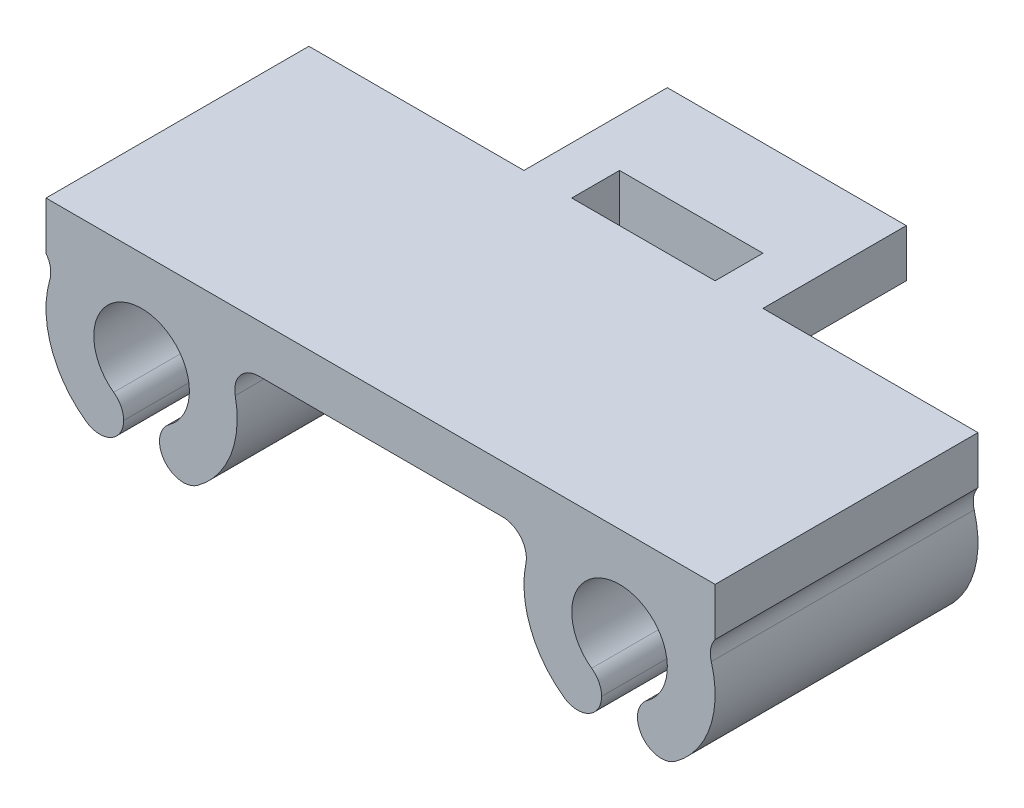
SolidWorks part; units mm, degrees
ref_plane "Front Plane" through (0, 0, 0) normal (0, 0, 1) x (1, 0, 0)
ref_plane "Top Plane" through (0, 0, 0) normal (0, 1, 0) x (1, 0, 0)
ref_plane "Right Plane" through (0, 0, 0) normal (1, 0, 0) x (0, 0, -1)
sketch "Sketch1" plane through (0, 0, 0) normal (0, 1, 0) x (1, 0, 0)
  line L1 (-14, -5.5) -> (14, -5.5)
  line L2 (-14, -5.5) -> (-14, 5.5)
  line L3 (-14, 5.5) -> (14, 5.5)
  line L4 (14, -5.5) -> (14, 5.5)
  line L5 (-14, -5.5) -> (14, 5.5) construction
  line L6 (-14, 5.5) -> (14, -5.5) construction
  line L7 (-5, 11.5) -> (5, 11.5)
  line L8 (-5, 11.5) -> (-5, 5.5)
  line L9 (-5, 5.5) -> (5, 5.5)
  line L10 (5, 11.5) -> (5, 5.5)
  line L11 (-5, 11.5) -> (5, 5.5) construction
  line L12 (-5, 5.5) -> (5, 11.5) construction
  line L13 (-3, 7.5) -> (3, 7.5)
  line L14 (-3, 7.5) -> (-3, 5.5)
  line L15 (-3, 5.5) -> (3, 5.5)
  line L16 (3, 7.5) -> (3, 5.5)
  line L17 (-3, 7.5) -> (3, 5.5) construction
  line L18 (-3, 5.5) -> (3, 7.5) construction
  point P0 (0, 0)
  point P6 (0, 8.5)
  point P12 (0, 6.5)
  dimension "D1" = 11
  dimension "D2" = 28
  dimension "D3" = 10
  dimension "D4" = 6
  dimension "D5" = 6
  dimension "D6" = 2
extrude "Boss-Extrude1" add sketch "Sketch1" along normal blind 2 contours L1 L4 L3 L2 | L10 L7 L8 L3 region at (0, 0, 0) region at (0, 0, -9)
sketch "Sketch2" plane through (0, 0, 0) normal (0, 0, 1) x (1, 0, 0)
  line L0 (-14, 0) -> (-5, 0) construction
  line L1 (-14, 2) -> (-14, 0) construction
  line L2 (-14, 2) -> (-5, 2) construction
  line L3 (0, 0) -> (0, -7.3036) construction
  line L5 (-10.75, -5.9291) -> (-10.75, -3.854)
  line L7 (-9.25, -5.9291) -> (-9.25, -3.854)
  line L8 (9.25, -5.9291) -> (9.25, -3.854)
  line L9 (10.75, -5.9291) -> (10.75, -3.854)
  arc A0 (-9.25, -3.854) -> (-10.75, -3.854) centre (-10, -2) ccw
  arc A1 (-9.25, -5.9291) -> (-10.75, -5.9291) centre (-10, -2) ccw
  arc A2 (9.25, -3.854) -> (10.75, -3.854) centre (10, -2) cw
  arc A3 (9.25, -5.9291) -> (10.75, -5.9291) centre (10, -2) cw
  point P9 (-9.5, -5.1816)
  dimension "D1" = 4
  dimension "D2" = 4
  dimension "D3" = 1.5
extrude "Boss-Extrude2" add sketch "Sketch2" along normal mid plane 11
fillet "Fillet1" radius 1 12 edges at (-13.4641, 0, 0) (13.4641, 0, 0) (-6.5359, 0, 0) (6.5359, 0, 0) (10.75, -5.9291, 0) (10.75, -3.854, 0) (9.25, -5.9291, 0) (9.25, -3.854, 0) (-9.25, -3.854, 0) (-10.75, -3.854, 0) (-9.25, -5.9291, 0) (-10.75, -5.9291, 0)
